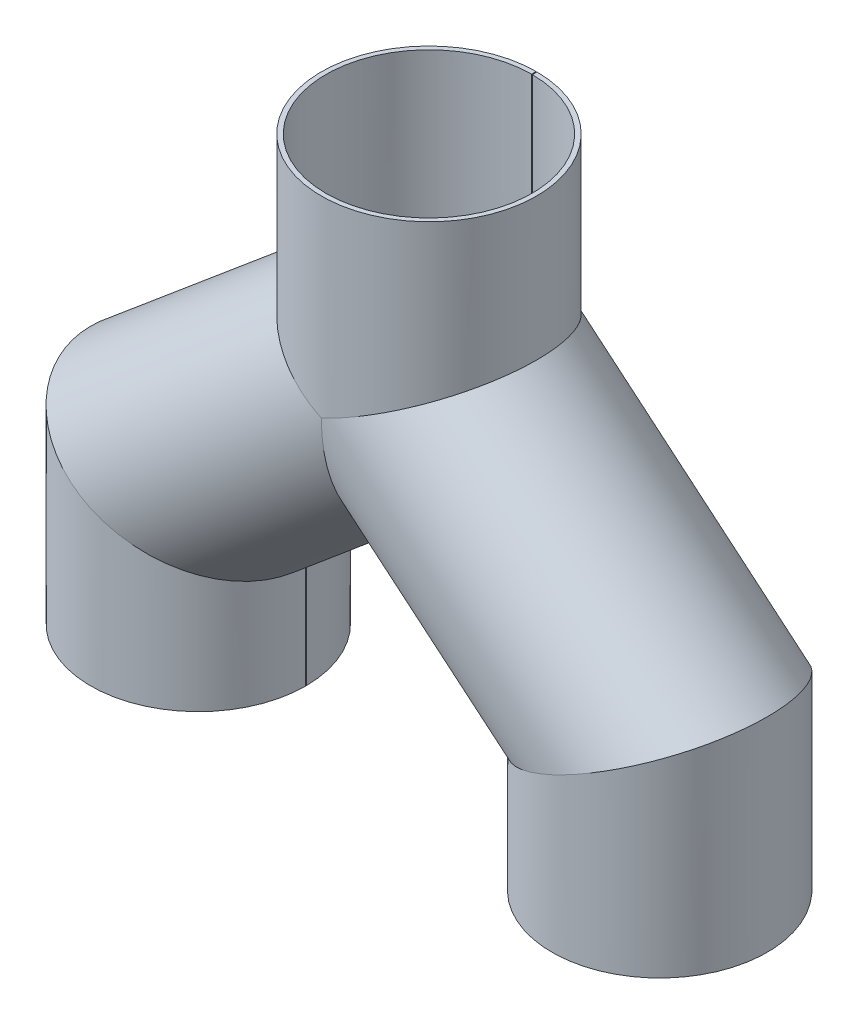
SolidWorks part; units mm, degrees
ref_plane "前视基准面" through (0, 0, 0) normal (0, 0, 1) x (1, 0, 0)
ref_plane "上视基准面" through (0, 0, 0) normal (0, 1, 0) x (1, 0, 0)
ref_plane "右视基准面" through (0, 0, 0) normal (1, 0, 0) x (0, 0, -1)
sketch "草图1" plane through (0, 0, 0) normal (0, 0, 1) x (1, 0, 0)
  line L0 (0, 250) -> (0, 0) construction
  line L1 (0, 0) -> (-300, -251.7299) construction
  line L2 (-300, -251.7299) -> (-300, -451.7299) construction
  line L3 (0, 0) -> (300, -251.7299) construction
  line L4 (300, -251.7299) -> (300, -451.7299) construction
  line L5 (0, 0) -> (0, -451.7299) construction
  line L6 (-140, 0) -> (140, 0) construction
  line L7 (0, -451.7299) -> (0, -457.7299) construction
  line L8 (389.9903, -144.4837) -> (210.0097, -358.9761) construction
  line L9 (160, -451.7299) -> (440, -451.7299) construction
  line L10 (440, -186.4468) -> (140, 65.2831) construction
  line L11 (140, 65.2831) -> (140, 250) construction
  line L12 (140, 250) -> (-140, 250) construction
  line L13 (440, -451.7299) -> (440, -186.4468) construction
  line L14 (160, -451.7299) -> (160, -317.013) construction
  line L15 (160, -317.013) -> (0, -182.757) construction
  line L16 (140, 65.2831) -> (0, 0) construction
  line L17 (0, -451.7299) -> (0, 250)
  line L18 (0, 0) -> (-140, 65.2831) construction
  dimension "d" = 280
  dimension "h1" = 250
  dimension "h2" = 200
  dimension "β" = 100
  dimension "t" = 6
  dimension "l" = 600
ref_plane "基准面1" through (440, -186.4468, 0) normal (0.766, -0.6428, 0) x (0, 0, -1)
ref_plane "基准面2" through (0, -451.7299, 0) normal (0, 1, 0) x (-1, 0, 0)
sketch "草图2" plane through (0, 0, 0) normal (0, 1, 0) x (1, 0, 0)
  line L0 (0, -140) -> (0, 140) construction
  circle A0 centre (0, 0) radius 140
sketch "草图3" plane through (440, -186.4468, 0) normal (0.766, -0.6428, 0) x (0, 0, -1)
  line L0 (0, 0) -> (0, -280) construction
  line L1 (-140, -140) -> (140, -140) construction
  circle A0 centre (0, -140) radius 140
sketch "草图4" plane through (0, -451.7299, 0) normal (0, 1, 0) x (-1, 0, 0)
  line L0 (-160, 0) -> (-440, 0) construction
  line L1 (-300, 140) -> (-300, -140) construction
  circle A0 centre (-300, 0) radius 140
extrude "拉伸-薄壁1" add sketch "草图2" along normal up to vertex (250 mm away) thin up to point (0, 250, 0) thin type one direction reverse wall 6
sketch "草图5" plane through (0, 0, 0) normal (0, 0, 1) x (1, 0, 0)
  line L0 (-536.1267, 250) -> (536.1267, -250)
  line L1 (0, 0) -> (-140, 65.2831) construction
extrude "切除-拉伸1" cut sketch "草图5" against normal through all and the other way through all flip side to cut
sketch "草图6" plane through (0, 0, 0) normal (0, 0, 1) x (1, 0, 0)
  line L0 (536.1267, 250) -> (-536.1267, -250)
  line L1 (140, 65.2831) -> (0, 0) construction
extrude "切除-拉伸2" cut sketch "草图6" against normal through all and the other way through all
extrude "拉伸-薄壁2" add sketch "草图3" against normal up to vertex (456.9053 mm away) separate body thin up to point (0, 0, 0) thin type one direction reverse wall 6
sketch "草图7" plane through (0, 0, 0) normal (0, 0, 1) x (1, 0, 0)
  line L0 (160, -317.013) -> (440, -186.4468)
extrude "切除-拉伸3" cut sketch "草图7" against normal through all and the other way through all flip side to cut
extrude "切除-拉伸6" cut sketch "草图6<2>" against normal through all and the other way through all flip side to cut
sketch "草图6<2>" plane through (0, 0, 0) normal (0, 0, 1) x (1, 0, 0) same geometry as "草图6"
extrude "切除-拉伸4" cut sketch "草图1" against normal through all and the other way through all
extrude "拉伸-薄壁3" add sketch "草图4" along normal up to vertex (265.2831 mm away) separate body thin up to point (440, -186.4468, 0) thin type one direction reverse wall 6
extrude "切除-拉伸5" cut sketch "草图7<2>" against normal through all and the other way through all
sketch "草图7<2>" plane through (0, 0, 0) normal (0, 0, 1) x (1, 0, 0) same geometry as "草图7"
extrude "切除-拉伸-薄壁1" cut sketch "草图1<2>" against normal through all thin thin type mid plane wall 1
sketch "草图1<2>" plane through (0, 0, 0) normal (0, 0, 1) x (1, 0, 0) same geometry as "草图1"
sketch "草图8" plane through (0, -451.7299, 0) normal (0, 1, 0) x (-1, 0, 0)
  line L0 (-300, 0) -> (-160, 0)
extrude "切除-拉伸-薄壁3" cut sketch "草图8" along normal through all thin thin type mid plane wall 1
sketch "草图9" plane through (440, -186.4468, 0) normal (0.766, -0.6428, 0) x (0, 0, -1)
  line L0 (0, -140) -> (0, -280)
extrude "切除-拉伸-薄壁4" cut sketch "草图9" against normal through all thin thin type mid plane wall 1
mirror "镜向1" about plane through (0, 0, 0) normal (1, 0, 0) of bodies 111 110
equation "\"D5@拉伸-薄壁1\" = \"t@草图1\""
equation "\"D5@拉伸-薄壁2\" = \"t@草图1\""
equation "\"D5@拉伸-薄壁3\" = \"t@草图1\""
